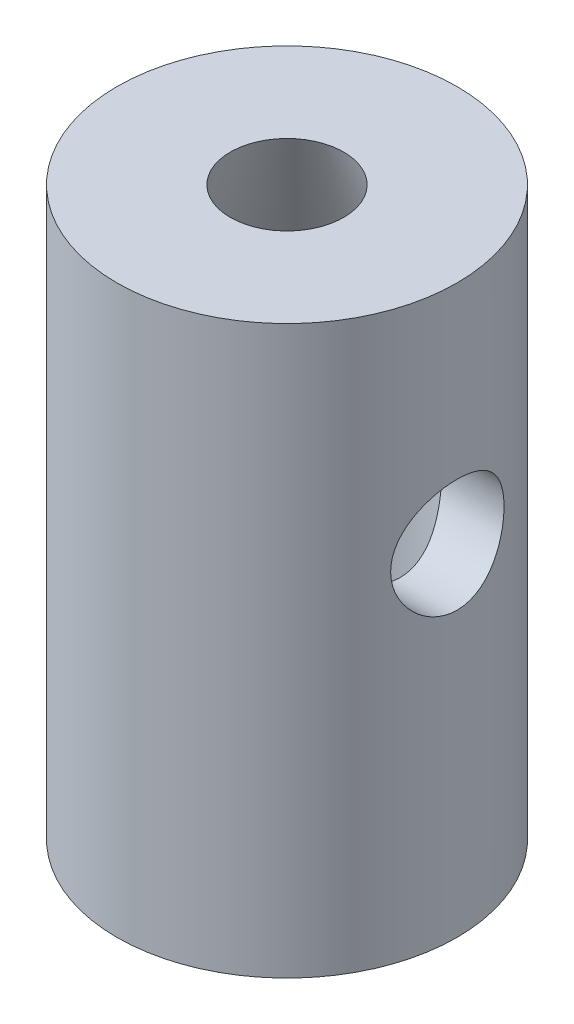
SolidWorks part; units mm, degrees
ref_plane "Front Plane" through (0, 0, 0) normal (0, 0, 1) x (1, 0, 0)
ref_plane "Top Plane" through (0, 0, 0) normal (0, 1, 0) x (1, 0, 0)
ref_plane "Right Plane" through (0, 0, 0) normal (1, 0, 0) x (0, 0, -1)
sketch "Sketch1" plane through (0, 0, 0) normal (0, 0, 1) x (1, 0, 0)
  line L0 (0, 0) -> (0, -127) construction
  line L1 (12.7, 0) -> (38.1, 0)
  line L2 (38.1, 0) -> (38.1, -127)
  line L3 (38.1, -127) -> (25.4, -127)
  line L4 (25.4, -127) -> (25.4, -34.893)
  line L5 (25.4, -34.893) -> (12.7, 0)
  dimension "D1" = 127
  dimension "D2" = 25.4
  dimension "D3" = 12.7
  dimension "D4" = 20
  dimension "D5" = 12.7
revolve "Revolve1" add sketch "Sketch1" angle 360 about L0
sketch "Sketch2" plane through (0, 0, 0) normal (1, 0, 0) x (0, 0, -1)
  line L0 (0, 0) -> (0, -50.8) construction
  circle A0 centre (0, -50.8) radius 12.7
  dimension "D1" = 25.4
  dimension "D2" = 50.8
extrude "Cut-Extrude1" cut sketch "Sketch2" along normal through all
